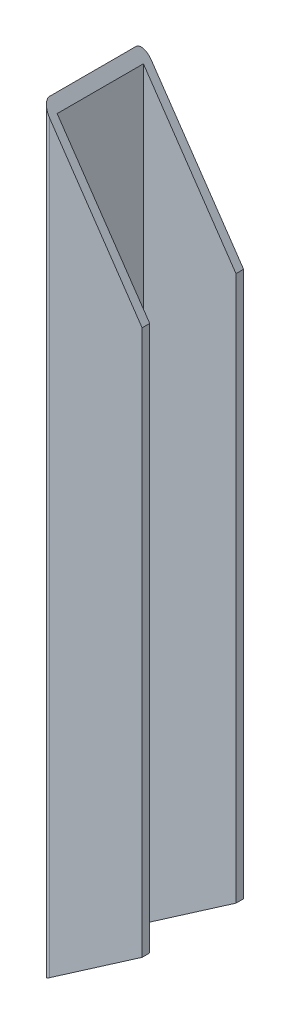
SolidWorks part; units mm, degrees
ref_plane "Спереди" through (0, 0, 0) normal (0, 0, 1) x (1, 0, 0)
ref_plane "Сверху" through (0, 0, 0) normal (0, 1, 0) x (1, 0, 0)
ref_plane "Справа" through (0, 0, 0) normal (1, 0, 0) x (0, 0, -1)
sketch "Эскиз1" plane through (0, 0, 0) normal (0, 1, 0) x (1, 0, 0)
  line L1 (-37, 20) -> (37, 20)
  line L2 (-40, 17) -> (-40, -17)
  line L3 (-37, -20) -> (37, -20)
  line L4 (40, 17) -> (40, -17)
  line L5 (-40, 20) -> (40, -20) construction
  line L6 (-40, -20) -> (40, 20) construction
  arc A0 (-37, 20) -> (-40, 17) centre (-37, 17) ccw
  arc A1 (-40, -17) -> (-37, -20) centre (-37, -17) ccw
  arc A2 (37, -20) -> (40, -17) centre (37, -17) ccw
  arc A3 (37, 20) -> (40, 17) centre (37, 17) cw
  point P0 (0, 0)
  dimension "D1" = 3
extrude "Вытянуть-Тонкостенный1" add sketch "Эскиз1" along normal blind 300 thin thin type one direction reverse wall 3
sketch "Эскиз2" plane through (0, 300, 0) normal (0, 1, 0) x (1, 0, 0)
  line L1 (-0.5, -21.5541) -> (41.1465, -21.5541)
  line L2 (-0.5, -21.5541) -> (-0.5, 20.9728)
  line L3 (-0.5, 20.9728) -> (41.1465, 20.9728)
  line L4 (41.1465, -21.5541) -> (41.1465, 20.9728)
extrude "Вырез-Вытянуть1" cut sketch "Эскиз2" against normal through all
sketch "Эскиз3" plane through (0, 0, 20) normal (0, 0, 1) x (1, 0, 0)
  line L0 (-40, 300) -> (-0.5, 242.2094)
  line L1 (-0.5, 0) -> (-0.5, 300) construction
  line L2 (-0.5, 242.2094) -> (-0.5, 27.2718)
  line L3 (-0.5, 27.2718) -> (-40, 0)
  line L4 (-40, 0) -> (-40, 300)
  point P5 (-0.5, 270.2826)
  point P9 (-0.5, 30.2901)
  point P10 (0, 0)
  point P11 (0, 0)
  point P12 (-0.5, 33.9244)
extrude "Вырез-Вытянуть2" cut sketch "Эскиз3" against normal through all flip side to cut
